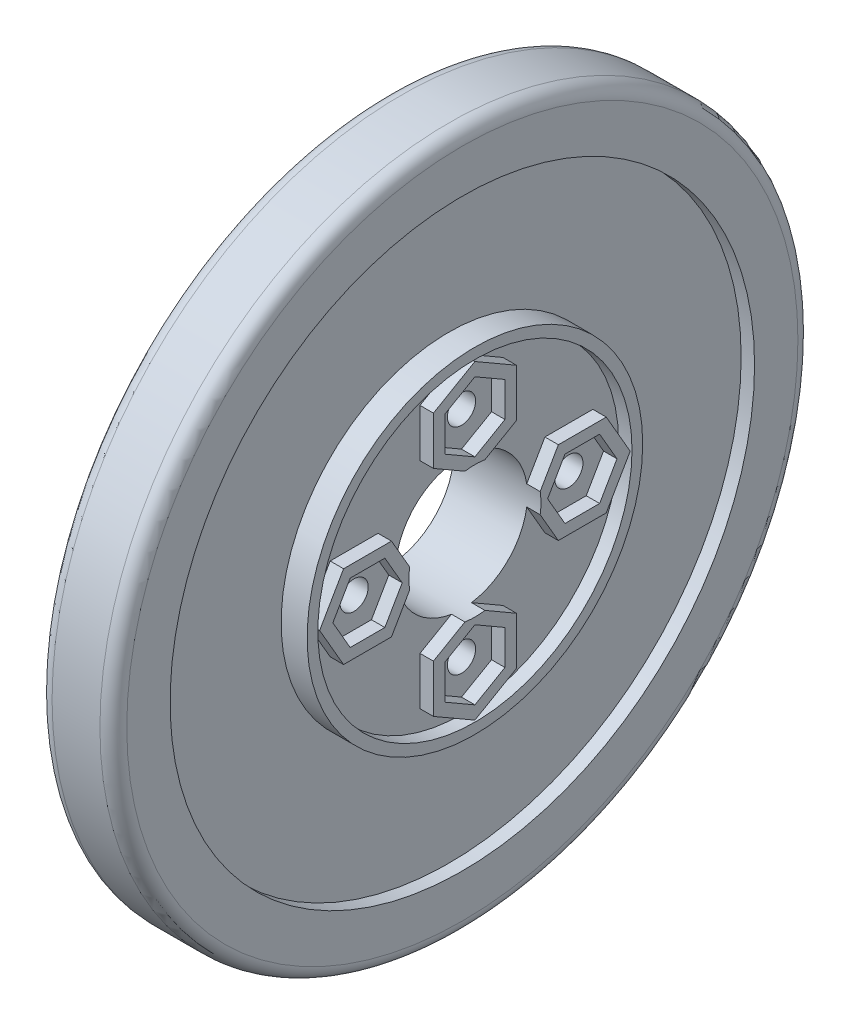
SolidWorks part; units mm, degrees
material "ABS PC"
ref_plane "Front Plane" through (0, 0, 0) normal (0, 0, 1) x (1, 0, 0)
ref_plane "Top Plane" through (0, 0, 0) normal (0, 1, 0) x (1, 0, 0)
ref_plane "Right Plane" through (0, 0, 0) normal (1, 0, 0) x (0, 0, -1)
sketch "Sketch1" plane through (0, 0, 0) normal (0, 1, 0) x (1, 0, 0)
  line L0 (0, 0) -> (0, 12.5)
  line L1 (6.5, 0) -> (0, 0)
  line L2 (0, 12.5) -> (6.5, 12.5)
  line L3 (6.5, 12.5) -> (6.5, 0)
  line L4 (0, 0) -> (0, 26)
  line L5 (0, 26) -> (5.5634, 26)
  line L6 (5.5634, 26) -> (5.5634, 12.5)
revolve "Revolve1" add sketch "Sketch1" angle 360 about L1 region at (3.25, 0, -6.25) region at (2.7817, 0, -19.25)
fillet "Fillet1" radius 1 2 edges at (0, 0, -26) (5.5634, 0, -26)
sketch "Sketch2" plane through (6.5, 0, 0) normal (1, 0, 0) x (0, 0, -1)
  line L0 (0, 0) -> (8, 0) construction
  line L1 (0, -5.4166) -> (-2.2373, -6.7083)
  line L2 (5.4166, 0) -> (6.7083, -2.2373)
  line L3 (6.7083, -2.2373) -> (9.2917, -2.2373)
  line L4 (9.2917, -2.2373) -> (10.5834, 0)
  line L5 (10.5834, 0) -> (9.2917, 2.2373)
  line L6 (9.2917, 2.2373) -> (6.7083, 2.2373)
  line L7 (6.7083, 2.2373) -> (5.4166, 0)
  line L8 (4.4317, 0) -> (6.2159, -3.0902)
  line L9 (6.2159, -3.0902) -> (9.7841, -3.0902)
  line L10 (9.7841, -3.0902) -> (11.5683, 0)
  line L11 (11.5683, 0) -> (9.7841, 3.0902)
  line L12 (9.7841, 3.0902) -> (6.2159, 3.0902)
  line L13 (6.2159, 3.0902) -> (4.4317, 0)
  line L14 (-2.2373, -6.7083) -> (-2.2373, -9.2917)
  line L15 (-2.2373, -9.2917) -> (0, -10.5834)
  line L16 (0, -10.5834) -> (2.2373, -9.2917)
  line L17 (2.2373, -9.2917) -> (2.2373, -6.7083)
  line L18 (2.2373, -6.7083) -> (0, -5.4166)
  line L19 (0, -4.4317) -> (-3.0902, -6.2159)
  line L20 (-3.0902, -6.2159) -> (-3.0902, -9.7841)
  line L21 (-3.0902, -9.7841) -> (0, -11.5683)
  line L22 (0, -11.5683) -> (3.0902, -9.7841)
  line L23 (3.0902, -9.7841) -> (3.0902, -6.2159)
  line L24 (3.0902, -6.2159) -> (0, -4.4317)
  line L25 (-5.4166, 0) -> (-6.7083, 2.2373)
  line L26 (-6.7083, 2.2373) -> (-9.2917, 2.2373)
  line L27 (-9.2917, 2.2373) -> (-10.5834, 0)
  line L28 (-10.5834, 0) -> (-9.2917, -2.2373)
  line L29 (-9.2917, -2.2373) -> (-6.7083, -2.2373)
  line L30 (-6.7083, -2.2373) -> (-5.4166, 0)
  line L31 (-4.4317, 0) -> (-6.2159, 3.0902)
  line L32 (-6.2159, 3.0902) -> (-9.7841, 3.0902)
  line L33 (-9.7841, 3.0902) -> (-11.5683, 0)
  line L34 (-11.5683, 0) -> (-9.7841, -3.0902)
  line L35 (-9.7841, -3.0902) -> (-6.2159, -3.0902)
  line L36 (-6.2159, -3.0902) -> (-4.4317, 0)
  line L37 (0, 5.4166) -> (2.2373, 6.7083)
  line L38 (2.2373, 6.7083) -> (2.2373, 9.2917)
  line L39 (2.2373, 9.2917) -> (0, 10.5834)
  line L40 (0, 10.5834) -> (-2.2373, 9.2917)
  line L41 (-2.2373, 9.2917) -> (-2.2373, 6.7083)
  line L42 (-2.2373, 6.7083) -> (0, 5.4166)
  line L43 (0, 4.4317) -> (3.0902, 6.2159)
  line L44 (3.0902, 6.2159) -> (3.0902, 9.7841)
  line L45 (3.0902, 9.7841) -> (0, 11.5683)
  line L46 (0, 11.5683) -> (-3.0902, 9.7841)
  line L47 (-3.0902, 9.7841) -> (-3.0902, 6.2159)
  line L48 (-3.0902, 6.2159) -> (0, 4.4317)
  circle A0 centre (8, 0) radius 1.05
  circle A1 centre (8, 0) radius 2.2373 construction
  circle A2 centre (8, 0) radius 3.0902 construction
  circle A3 centre (0, -8) radius 1.05
  circle A4 centre (0, -8) radius 2.2373 construction
  circle A5 centre (0, -8) radius 3.0902 construction
  circle A6 centre (-8, 0) radius 1.05
  circle A7 centre (-8, 0) radius 2.2373 construction
  circle A8 centre (-8, 0) radius 3.0902 construction
  circle A9 centre (0, 8) radius 1.05
  circle A10 centre (0, 8) radius 2.2373 construction
  circle A11 centre (0, 8) radius 3.0902 construction
  circle A12 centre (0, 0) radius 11.7041
  circle A13 centre (0, 0) radius 4.919
  point P68 (0, 0)
  dimension "D1" = 4
extrude "Cut-Extrude1" cut sketch "Sketch2" against normal blind 1 contours A12 L13 L12 L11 L10 L9 L8 L24 L23 L22 L21 L20 L19 L36 L35 L34 L33 L32 L31 L48 L47 L46 L45 L44 L43 | L41 L42 L37 L38 L39 L40 A9 | L17 L18 L1 L14 L15 L16 A3 | L29 L30 L25 L26 L27 L28 A6 | L6 L7 L2 L3 L4 L5 A0 region at (6.5, -6.1216, -1.0845) region at (6.5, 1.0845, -6.1216) region at (6.5, -1.0845, 6.1216) region at (6.5, 6.1216, 1.0845) region at (6.5, 0, 11.671)
extrude "Cut-Extrude2" cut sketch "Sketch2<3>" against normal through all contours A9 | A0 | A3 | A6 | L13 A13 L43 L48 L31 L36 L19 L24 L8 | L19 A13 L24 | L31 A13 L36 | L43 A13 L48 | L8 A13 L13 region at (6.5, 0, -4.7436) region at (6.5, 0, 0) region at (6.5, -4.7436, 0) region at (6.5, 4.7436, 0) region at (6.5, 0, 4.7436) region at (6.5, 0, -8) region at (6.5, -8, 0) region at (6.5, 0, 8) region at (6.5, 8, 0)
sketch "Sketch2<3>" plane through (6.5, 0, 0) normal (1, 0, 0) x (0, 0, -1) same geometry as "Sketch2"
sketch "Sketch3" plane through (0, 0, 0) normal (-1, 0, 0) x (0, 0, 1)
  circle A0 centre (0, 0) radius 21.7716
  circle A1 centre (0, 0) radius 12.5
extrude "Cut-Extrude3" cut sketch "Sketch3" against normal blind 1
sketch "Sketch4" plane through (5.5634, 0, 0) normal (1, 0, 0) x (0, 0, -1)
  circle A0 centre (0, 0) radius 12.5
  circle A2 centre (0, 0) radius 21.7716
extrude "Cut-Extrude4" cut sketch "Sketch4" against normal blind 1
